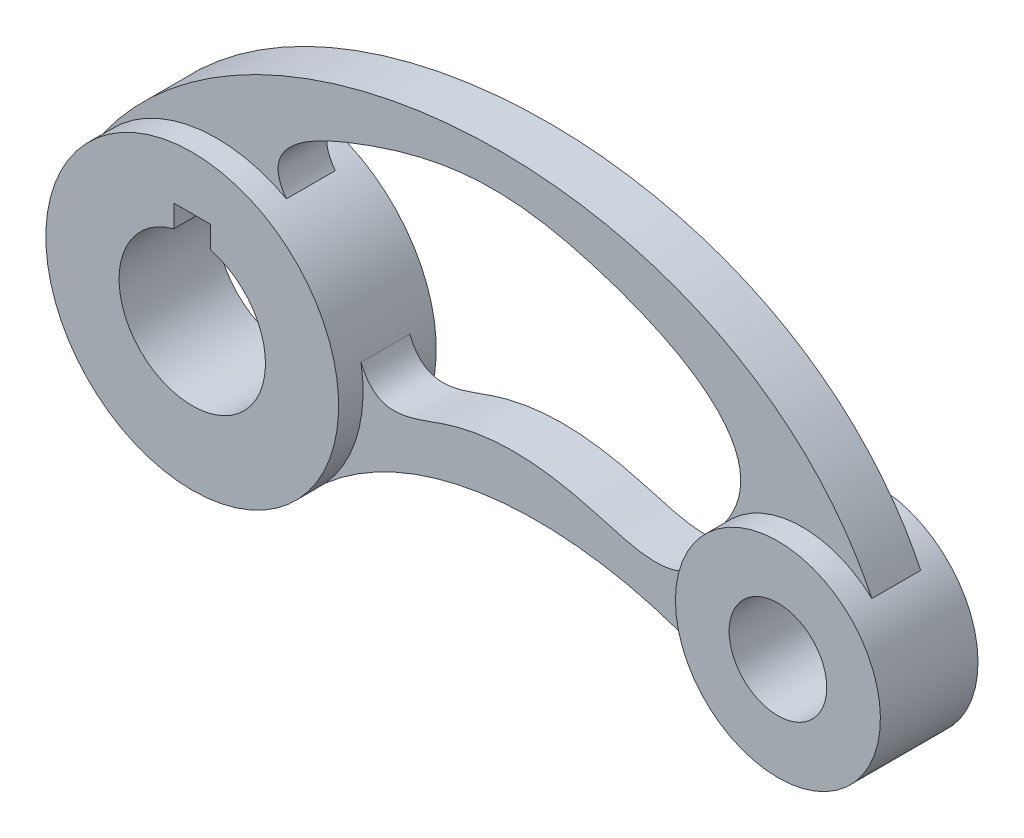
SolidWorks part; units mm, degrees
ref_plane "Front Plane" through (0, 0, 0) normal (0, 0, 1) x (1, 0, 0)
ref_plane "Top Plane" through (0, 0, 0) normal (0, 1, 0) x (1, 0, 0)
ref_plane "Right Plane" through (0, 0, 0) normal (1, 0, 0) x (0, 0, -1)
sketch "Sketch1" plane through (0, 0, 0) normal (0, 0, 1) x (1, 0, 0)
  line L0 (0, 0) -> (0, 68.6786) construction
  line L1 (0.5052, 0.1921) -> (72.7195, 0.1921) construction
  line L2 (-87.8998, 14.7064) -> (-87.8998, 19.276)
  line L5 (-87.8998, 19.276) -> (-95.4726, 19.276)
  line L7 (-62.1049, 5.187) -> (-62.1055, 5.187)
  line L11 (-95.4726, 14.7064) -> (-95.4726, 19.276)
  circle A0 centre (-91.6862, 0.1921) radius 30
  circle A1 centre (28.3138, 0.1921) radius 21
  arc A2 (-95.4726, 14.7064) -> (-87.8998, 14.7064) centre (-91.6862, 0.1921) ccw
  circle A3 centre (28.3138, 0.1921) radius 10
  spline S0 degree 3 poles (-117.2097, 15.9577) (-84.6754, 68.5009) (15.0574, 72.7651) (42.5666, 15.6148) knots 0 0 0 0 1 1 1 1
  spline S1 degree 3 poles (-69.3616, -19.8482) (-47.0164, -0.4487) (-12.2074, -1.381) (13.049, -14.2296) knots 0 0 0 0 1 1 1 1
  spline S2 degree 3 poles (-77.3866, 26.5649) (-83.4323, 34.665) (-50.6284, 50.5652) (-17.6555, 51.5644) (25.2467, 29.6095) (11.1123, 12.2383) knots 0 0 0 0 0.204044 0.600639 1 1 1 1
  spline S3 degree 3 poles (-62.1049, 5.187) (-58.6015, -3.264) (-40.9158, 6.6053) (-17.3642, 4.8569) (1.3729, -2.887) (7.6675, 4.0299) knots 0 0 0 0 0.265783 0.675205 1 1 1 1
  point P9 (0, 0)
  point P16 (0, 0)
  point P24 (0, 0)
  point P30 (0, 0)
  dimension "D1" = 60
  dimension "D2" = 42
  dimension "D4" = 30
  dimension "D5" = 20
  dimension "D3" = 120
extrude "Boss-Extrude3" add sketch "Sketch1" along normal blind 10 and the other way blind 10 contours S0 A0 A2 L11 L5 L2 region at (-64.4631, -10.2343, 0)
extrude "Boss-Extrude4" add sketch "Sketch1<6>" along normal blind 10 and the other way blind 10 separate body contours A1 S2 A3 region at (9.4977, 8.0889, 0)
sketch "Sketch1<6>" plane through (0, 0, 0) normal (0, 0, 1) x (1, 0, 0) same geometry as "Sketch1"
extrude "Boss-Extrude5" add sketch "Sketch1<7>" along normal blind 5 and the other way blind 5 contours A0 S2 A1 S0 region at (-99.8338, 30.781, 0)
sketch "Sketch1<7>" plane through (0, 0, 0) normal (0, 0, 1) x (1, 0, 0) same geometry as "Sketch1"
extrude "Boss-Extrude6" add sketch "Sketch1<9>" along normal blind 5 and the other way blind 5 contours S3 A0 S1 A1 region at (-29.1094, -3.1412, 0)
sketch "Sketch1<9>" plane through (0, 0, 0) normal (0, 0, 1) x (1, 0, 0) same geometry as "Sketch1"
